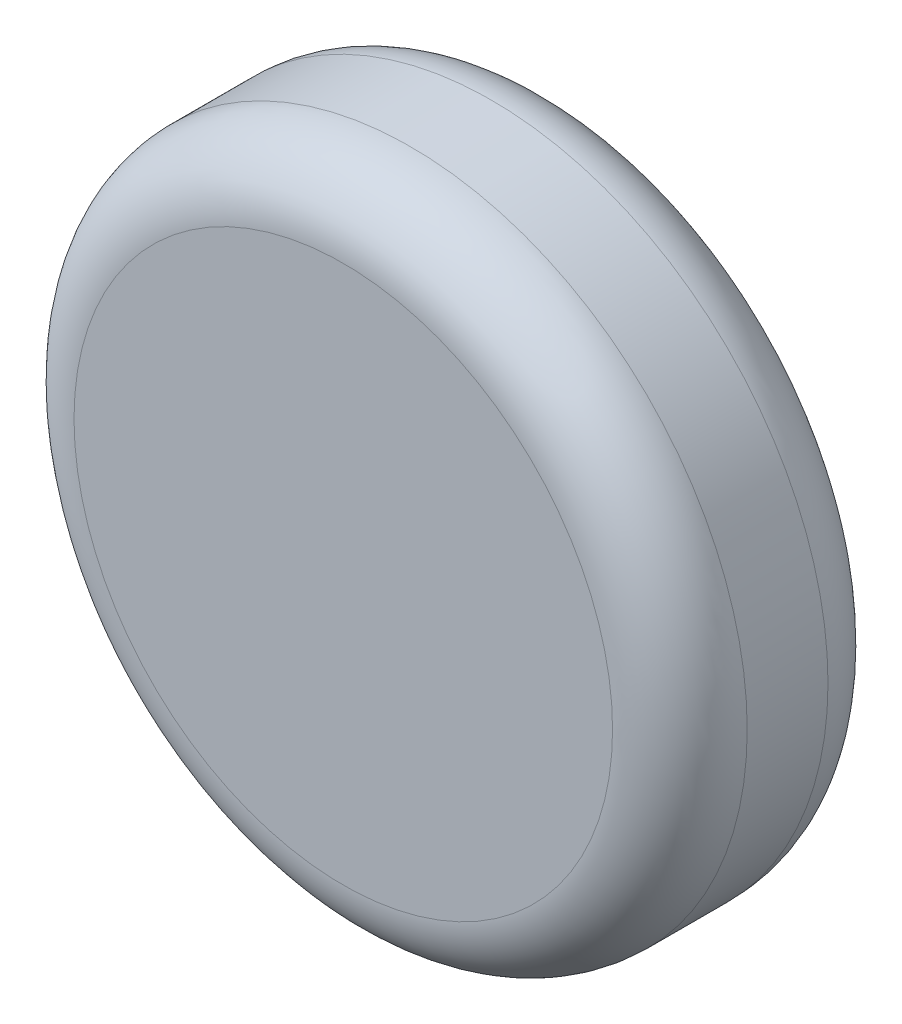
SolidWorks part; units mm, degrees
ref_plane "Спереди" through (0, 0, 0) normal (0, 0, 1) x (1, 0, 0)
ref_plane "Сверху" through (0, 0, 0) normal (0, 1, 0) x (1, 0, 0)
ref_plane "Справа" through (0, 0, 0) normal (1, 0, 0) x (0, 0, -1)
sketch "Эскиз1" plane through (0, 0, 0) normal (0, 0, 1) x (1, 0, 0)
  circle A0 centre (0, 0) radius 50
  dimension "D1" = 100
extrude "Бобышка-Вытянуть1" add sketch "Эскиз1" along normal blind 32
fillet "Скругление1" radius 10 2 edges at (50, 0, 0) (50, 0, 32)
sketch "Эскиз2" plane through (0, 0, 0) normal (0, 0, -1) x (-1, 0, 0)
  line L0 (-1.199, 2.75) -> (1.199, 2.75)
  line L7 (-1.199, -2.75) -> (1.199, -2.75)
  circle A0 centre (0, 0) radius 5
  arc A1 (-1.199, 2.75) -> (-1.199, -2.75) centre (0, 0) ccw
  arc A4 (1.199, -2.75) -> (1.199, 2.75) centre (0, 0) ccw
  dimension "D1" = 10
  dimension "D2" = 6
  dimension "D4" = 2.3979
  dimension "D5" = 2.3979
extrude "Бобышка-Вытянуть2" add sketch "Эскиз2" along normal blind 25
